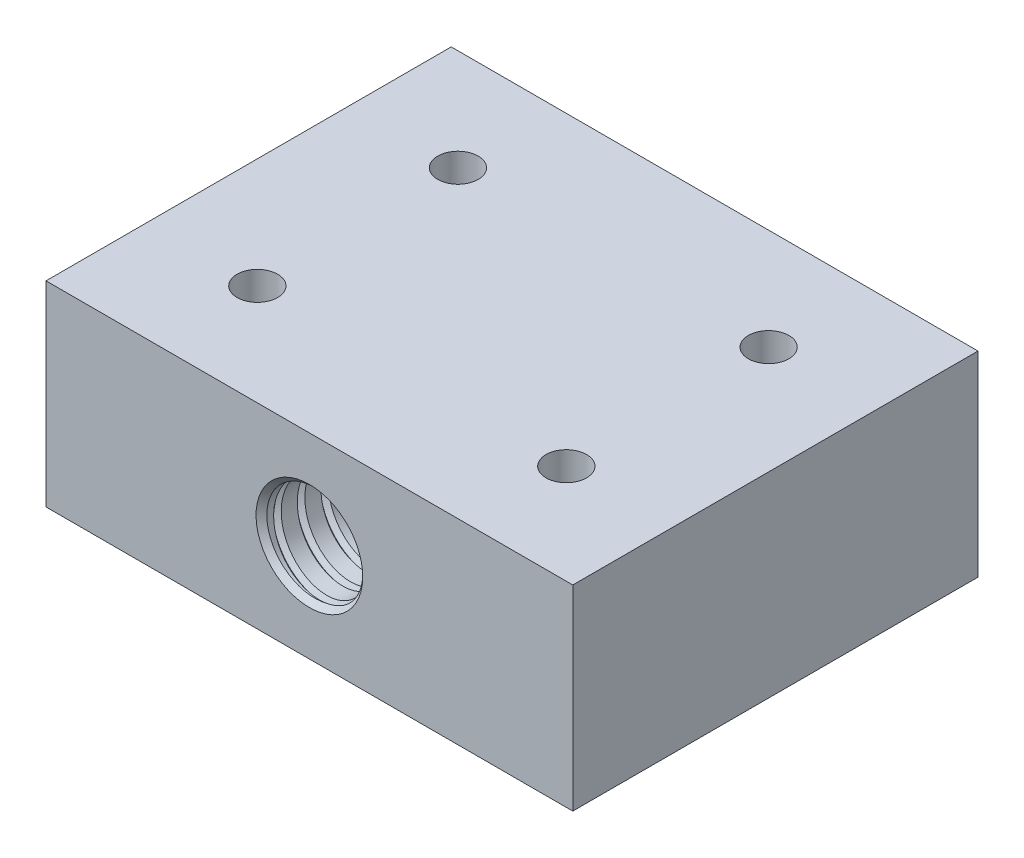
SolidWorks part; units mm, degrees
ref_plane "Front Plane" through (0, 0, 0) normal (0, 0, 1) x (1, 0, 0)
ref_plane "Top Plane" through (0, 0, 0) normal (0, 1, 0) x (1, 0, 0)
ref_plane "Right Plane" through (0, 0, 0) normal (1, 0, 0) x (0, 0, -1)
sketch "Sketch2" plane through (0, 0, 0) normal (0, 1, 0) x (1, 0, 0)
  line L1 (-39, -30) -> (39, -30)
  line L2 (-39, -30) -> (-39, 30)
  line L3 (-39, 30) -> (39, 30)
  line L4 (39, -30) -> (39, 30)
  line L5 (-39, -30) -> (39, 30) construction
  line L6 (-39, 30) -> (39, -30) construction
  point P0 (0, 0)
  dimension "D1" = 78
  dimension "D2" = 60
extrude "Boss-Extrude2" add sketch "Sketch2" along normal blind 29
sketch "Sketch3" plane through (0, 0, 0) normal (0, -1, 0) x (1, 0, 0)
  circle A0 centre (-29.1, -15.5) radius 4
  circle A1 centre (-29.1, 15.5) radius 4
  circle A2 centre (29.1, 15.5) radius 4
  circle A3 centre (29.1, -15.5) radius 4
  point P6 (-29.1, 15.5)
  point P7 (29.1, 15.5)
  point P8 (29.1, -15.5)
  point P9 (-29.1, -15.5)
  dimension "D9" = 8
  dimension "D10" = 8
  dimension "D11" = 8
  dimension "D12" = 8
  dimension "D1" = 58.2
  dimension "D2" = 58.2
  dimension "D3" = 31
  dimension "D4" = 31
sketch "Sketch4" plane through (0, 0, 30) normal (0, 0, 1) x (1, 0, 0)
  circle A0 centre (0, 14.5) radius 7.1
  point P6 (0, 14.5)
  dimension "D1" = 14.2
extrude "Cut-Extrude1" cut sketch "Sketch4" against normal through all
chamfer "Chamfer1" distance 0.8 angle 45 2 edges at (7.1, 14.5, 30) (7.1, 14.5, -30)
sketch "Sketch8" plane through (0, 29, 0) normal (0, 1, 0) x (1, 0, 0)
  line L0 (-39, 30) -> (-39, -30) construction
  line L1 (-39, -30) -> (39, -30) construction
  circle A0 centre (-23, 15) radius 3
  circle A1 centre (23, 15) radius 3
  circle A2 centre (23.2924, -15.2498) radius 3
  circle A3 centre (-22.7076, -15) radius 3
  point P0 (-23, 15)
  point P1 (23, 15)
  point P2 (23.2924, -15.2498)
  point P3 (-22.7076, -15)
  dimension "D6" = 6
  dimension "D7" = 6
  dimension "D8" = 6
  dimension "D9" = 6
  dimension "D1" = 46
  dimension "D2" = 46
  dimension "D3" = 30
  dimension "D4" = 16
  dimension "D5" = 15
extrude "Cut-Extrude2" cut sketch "Sketch8" against normal blind 20
thread "Thread1" pitch 1.5 method cut profile "Thread Profile2" start angle 0, offset 5, length 0, pitch 3.5, diameter 14.2
ref_plane "Plane2" through (7.1, 14.5, -34.2) normal (0, -1, 0) x (1, 0, 0)
sketch "Thread Profile2" plane through (7.1, 14.5, -34.2) normal (0, -1, 0) x (1, 0, 0)
  line L0 (0, 0) -> (0, 1.5) construction
  line L1 (0, 0) -> (0.8119, 0.4687)
  line L2 (0.8119, 0.4687) -> (0.8119, 0.6562)
  line L3 (0.8119, 0.6562) -> (0, 1.125)
  line L4 (0.8119, 0.5625) -> (0, 0.5625) construction
  line L11 (0, 0) -> (0, 1.125)
  point P2 (0, 0)
  dimension "Pitch" = 1.5
  dimension "Profile_Angle" = 60
  dimension "Profile_Land" = 0.1875
  dimension "Profile_Height" = 0.8119
